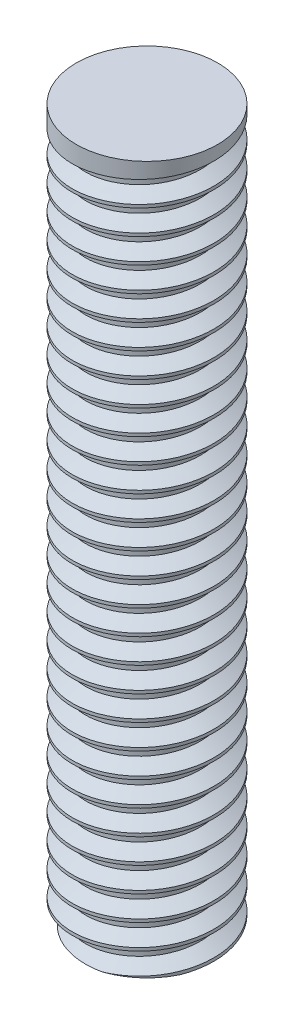
SolidWorks part; units mm, degrees
material "AISI 1020"
ref_plane "Front Plane" through (0, 0, 0) normal (0, 0, 1) x (1, 0, 0)
ref_plane "Top Plane" through (0, 0, 0) normal (0, 1, 0) x (1, 0, 0)
ref_plane "Right Plane" through (0, 0, 0) normal (1, 0, 0) x (0, 0, -1)
sketch "Sketch1" plane through (0, 0, 0) normal (0, 1, 0) x (1, 0, 0)
  circle A0 centre (0, 0) radius 2
  dimension "D1" = 4
extrude "Boss-Extrude1" add sketch "Sketch1" along normal blind 20
thread "Thread1" pitch 0.7 method cut profile "Thread Profile1" start angle 0, offset 0, length 0, pitch 0.7, diameter 4
ref_plane "Plane1" through (-2, 20, 0) normal (0, 0, 1) x (-1, 0, 0)
sketch "Thread Profile1" plane through (-2, 20, 0) normal (0, 0, 1) x (-1, 0, 0)
  line L0 (0, 0) -> (0, 0.7) construction
  line L11 (0, 0) -> (0, 0.6125)
  line L12 (0, 0.6125) -> (-0.3789, 0.3937)
  line L13 (-0.3789, 0.3937) -> (-0.3789, 0.2187)
  line L15 (-0.3789, 0.2187) -> (0, 0)
  line L17 (-0.3789, 0.3062) -> (0, 0.3062) construction
  point P2 (0, 0)
  dimension "Pitch" = 0.7
  dimension "Profile_Angle" = 60
  dimension "Profile_Land" = 0.175
  dimension "Profile_Height" = 0.3789
